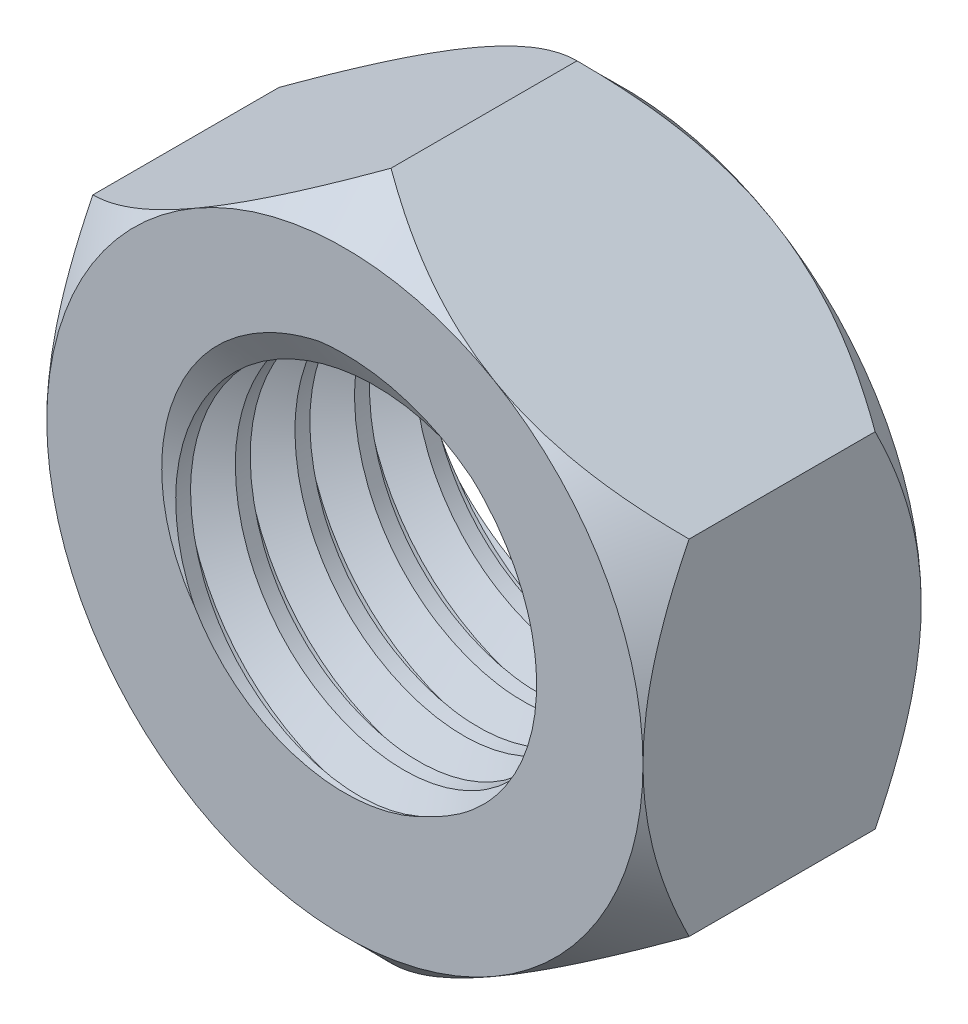
SolidWorks part; units mm, degrees
material "AISI 304"
ref_plane "Front Plane" through (0, 0, 0) normal (0, 0, 1) x (1, 0, 0)
ref_plane "Top Plane" through (0, 0, 0) normal (0, 1, 0) x (1, 0, 0)
ref_plane "Right Plane" through (0, 0, 0) normal (1, 0, 0) x (0, 0, -1)
sketch "Sketch1" plane through (0, 0, 0) normal (0, 0, 1) x (1, 0, 0)
  line L1 (0, -3.4641) -> (3, -1.7321)
  line L2 (3, -1.7321) -> (3, 1.7321)
  line L3 (3, 1.7321) -> (0, 3.4641)
  line L4 (0, 3.4641) -> (-3, 1.7321)
  line L5 (-3, 1.7321) -> (-3, -1.7321)
  line L6 (-3, -1.7321) -> (0, -3.4641)
  circle A0 centre (0, 0) radius 3 construction
  circle A1 centre (0, 0) radius 1.75
  dimension "D1" = 3.5
  dimension "D2" = 6
extrude "Boss-Extrude1" add sketch "Sketch1" along normal mid plane 2.8
sketch "Sketch3" plane through (0, 0, 1.4) normal (0, 0, 1) x (1, 0, 0)
  circle A0 centre (0, 0) radius 3
extrude "Cut-Extrude1" cut sketch "Sketch3" against normal blind 2.8 draft 45 flip side to cut
mirror "Mirror1" about plane through (0, 0, 0) normal (0, 0, 1) of "Cut-Extrude1"
thread "Thread1" pitch 0.6 method cut trim with start face yes trim with end face yes profile "Thread Profile1" start angle 0, offset 1, length 0, pitch 0.6, diameter 3.5
ref_plane "Plane1" through (-1.75, 0, 2.4) normal (0, -1, 0) x (-1, 0, 0)
sketch "Thread Profile1" plane through (-1.75, 0, 2.4) normal (0, -1, 0) x (-1, 0, 0)
  line L0 (0, 0) -> (0, 0.6) construction
  line L1 (0, 0) -> (0.3248, 0.1875)
  line L2 (0.3248, 0.1875) -> (0.3248, 0.2625)
  line L3 (0.3248, 0.2625) -> (0, 0.45)
  line L4 (0.3248, 0.225) -> (0, 0.225) construction
  line L11 (0, 0) -> (0, 0.45)
  point P2 (0, 0)
  dimension "Pitch" = 0.6
  dimension "Profile_Angle" = 60
  dimension "Profile_Land" = 0.075
  dimension "Profile_Height" = 0.3248
